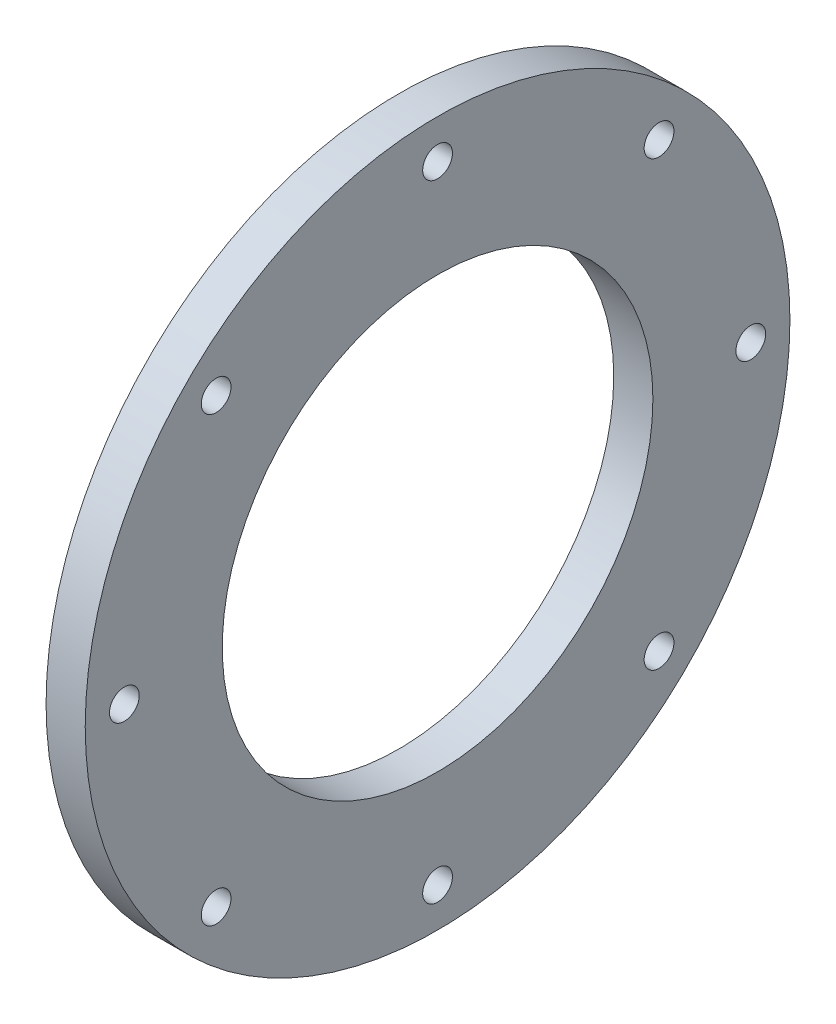
SolidWorks part; units mm, degrees
material "7075-T6 (SN)"
ref_plane "Front Plane" through (0, 0, 0) normal (0, 0, 1) x (1, 0, 0)
ref_plane "Top Plane" through (0, 0, 0) normal (0, 1, 0) x (1, 0, 0)
ref_plane "Right Plane" through (0, 0, 0) normal (1, 0, 0) x (0, 0, -1)
sketch "Sketch1" plane through (0, 0, 0) normal (1, 0, 0) x (0, 0, -1)
  circle A0 centre (0, 0) radius 34.925
  circle A1 centre (0, 0) radius 57.15
  dimension "D1" = 69.85
  dimension "D2" = 114.3
extrude "Boss-Extrude1" add sketch "Sketch1" along normal blind 6.35
sketch "Sketch2" plane through (6.35, 0, 0) normal (1, 0, 0) x (0, 0, -1)
  circle A0 centre (0, 0) radius 50.8 construction
  circle A1 centre (0, 50.8) radius 2.413
  circle A2 centre (35.921, 35.921) radius 2.413
  circle A3 centre (50.8, 0) radius 2.413
  circle A4 centre (35.921, -35.921) radius 2.413
  circle A5 centre (0, -50.8) radius 2.413
  circle A6 centre (-35.921, -35.921) radius 2.413
  circle A7 centre (-50.8, 0) radius 2.413
  circle A8 centre (-35.921, 35.921) radius 2.413
  point P21 (0, 0)
  dimension "D1" = 101.6
  dimension "D2" = 4.826
  dimension "D3" = 8
extrude "Cut-Extrude1" cut sketch "Sketch2" against normal through all
